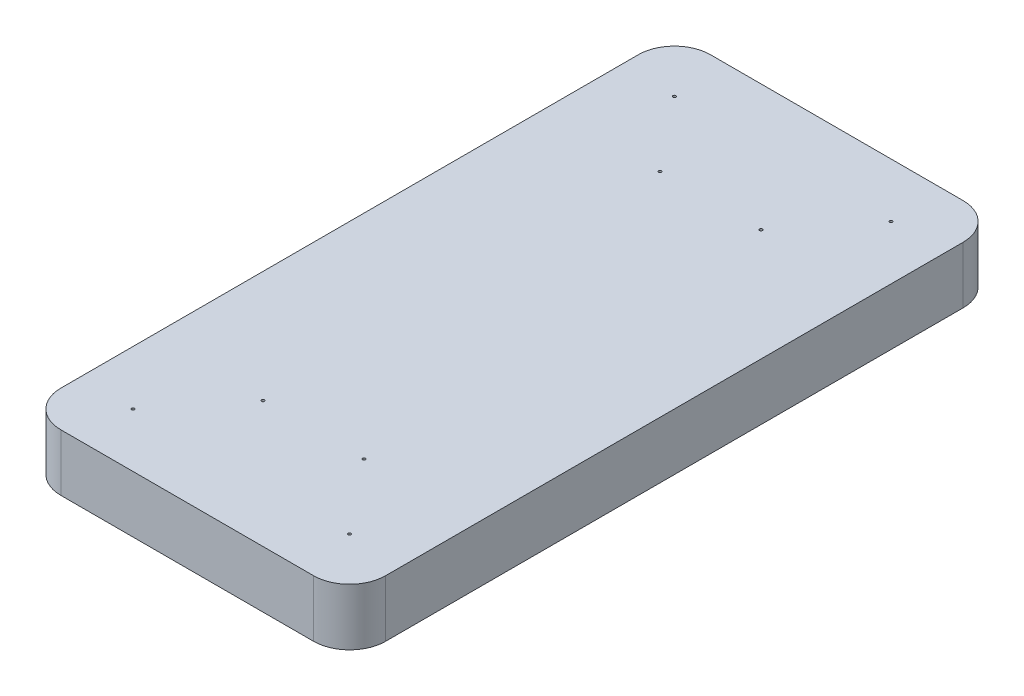
SolidWorks part; units mm, degrees
ref_plane "Front Plane" through (0, 0, 0) normal (0, 0, 1) x (1, 0, 0)
ref_plane "Top Plane" through (0, 0, 0) normal (0, 1, 0) x (1, 0, 0)
ref_plane "Right Plane" through (0, 0, 0) normal (1, 0, 0) x (0, 0, -1)
sketch "Sketch1" plane through (0, 0, 0) normal (0, 1, 0) x (1, 0, 0)
  line L1 (0, 0) -> (114.3, 0)
  line L2 (0, 0) -> (0, 228.6)
  line L3 (0, 228.6) -> (114.3, 228.6)
  line L4 (114.3, 0) -> (114.3, 228.6)
  dimension "9" = 228.6
  dimension "5.5" = 114.3
extrude "Boss-Extrude2" add sketch "Sketch1" along normal blind 20
sketch "Sketch4" plane through (0, 20, -20) normal (0, -1, 0) x (1, 0, 0)
  line L0 (114.3, -296.7063) -> (-114.3, -296.7063) construction
  line L1 (114.3, -265.75) -> (-114.3, -265.75) construction
  line L2 (114.3, -322.9) -> (-114.3, -322.9)
  line L3 (114.3, -322.9) -> (114.3, -208.6)
  line L4 (114.3, -208.6) -> (-114.3, -208.6)
  line L5 (-114.3, -322.9) -> (-114.3, -208.6)
  line L7 (0, 20) -> (114.3, 20) construction
  line L9 (0, -208.6) -> (0, 20) construction
  circle A0 centre (83.3438, -296.7063) radius 3.1
  circle A1 centre (-96.0437, -296.7063) radius 3.1
  circle A2 centre (83.3437, -234.7938) radius 3.1
  circle A3 centre (-96.0438, -234.7937) radius 3.1
  dimension "D2" = 6.2
  dimension "D3" = 30.9562
  dimension "D1" = 30.9562
  dimension "D4" = 2
sketch "Sketch5" plane through (0, 20, 0) normal (0, 1, 0) x (1, 0, 0)
  line L0 (57.15, 0) -> (57.15, 228.6) construction
  line L1 (0, 0) -> (114.3, 0) construction
  line L2 (114.3, 228.6) -> (-114.3, 228.6) construction
  line L11 (19.05, 209.55) -> (19.05, 19.05)
  line L12 (19.05, 19.05) -> (95.25, 19.05)
  line L13 (95.25, 19.05) -> (95.25, 209.55)
  line L14 (95.25, 209.55) -> (19.05, 209.55)
  line L15 (19.05, 209.55) -> (19.05, 19.05)
  line L16 (19.05, 19.05) -> (95.25, 19.05)
  line L17 (95.25, 19.05) -> (95.25, 209.55)
  line L18 (95.25, 209.55) -> (19.05, 209.55)
  circle A0 centre (95.25, 209.55) radius 0.5
  circle A1 centre (95.25, 19.05) radius 0.5
  circle A2 centre (19.05, 19.05) radius 0.5
  circle A3 centre (19.05, 209.55) radius 0.5
  dimension "D2" = 1
  dimension "D3" = 1
  dimension "D4" = 1
  dimension "D5" = 1
  dimension "D1" = 19.05
extrude "Cut-Extrude1" cut sketch "Sketch5" against normal through all contours L17 A0 L18 | L18 A0 L17 | L16 A1 L17 | L17 A1 L16 | L15 A2 L16 | L16 A2 L15 | L15 A3 L18 | L18 A3 L15 region at (19.2622, 20, -209.3378) region at (18.9793, 20, -209.6207) region at (19.2622, 20, -19.2622) region at (18.9793, 20, -18.9793) region at (95.3207, 20, -209.6207) region at (95.0378, 20, -209.3378) region at (95.0378, 20, -19.2622) region at (95.3207, 20, -18.9793)
sketch "Sketch6" plane through (0, 0, 0) normal (0, -1, 0) x (1, 0, 0)
  line L1 (74.93, -184.15) -> (39.37, -184.15)
  line L2 (74.93, -184.15) -> (74.93, -44.45)
  line L3 (74.93, -44.45) -> (39.37, -44.45)
  line L4 (39.37, -184.15) -> (39.37, -44.45)
  circle A0 centre (95.25, -209.55) radius 0.5 construction
  circle A2 centre (74.93, -184.15) radius 0.5
  circle A3 centre (39.37, -184.15) radius 0.5
  circle A4 centre (39.37, -44.45) radius 0.5
  circle A5 centre (74.93, -44.45) radius 0.5
  dimension "D5" = 1
  dimension "D6" = 1
  dimension "D7" = 1
  dimension "D8" = 1
  dimension "D1" = 139.7
  dimension "D2" = 35.56
  dimension "D3" = 25.4
  dimension "D4" = 20.32
extrude "Cut-Extrude2" cut sketch "Sketch6" against normal through all contours L1 A2 L2 | L2 A2 L1 | L4 A3 L1 | L1 A3 L4 | L3 A4 L4 | L4 A4 L3 | L3 A5 L2 | L2 A5 L3 region at (39.2993, 0, -184.2207) region at (39.5822, 0, -183.9378) region at (74.7178, 0, -183.9378) region at (75.0007, 0, -184.2207) region at (39.2993, 0, -44.3793) region at (39.5822, 0, -44.6622) region at (74.7178, 0, -44.6622) region at (75.0007, 0, -44.3793)
fillet "Fillet1" radius 12.7 4 edges at (0, 10, -228.6) (114.3, 10, 0) (0, 10, 0) (114.3, 10, -228.6)
equation "\"2c\"=0.787402"
